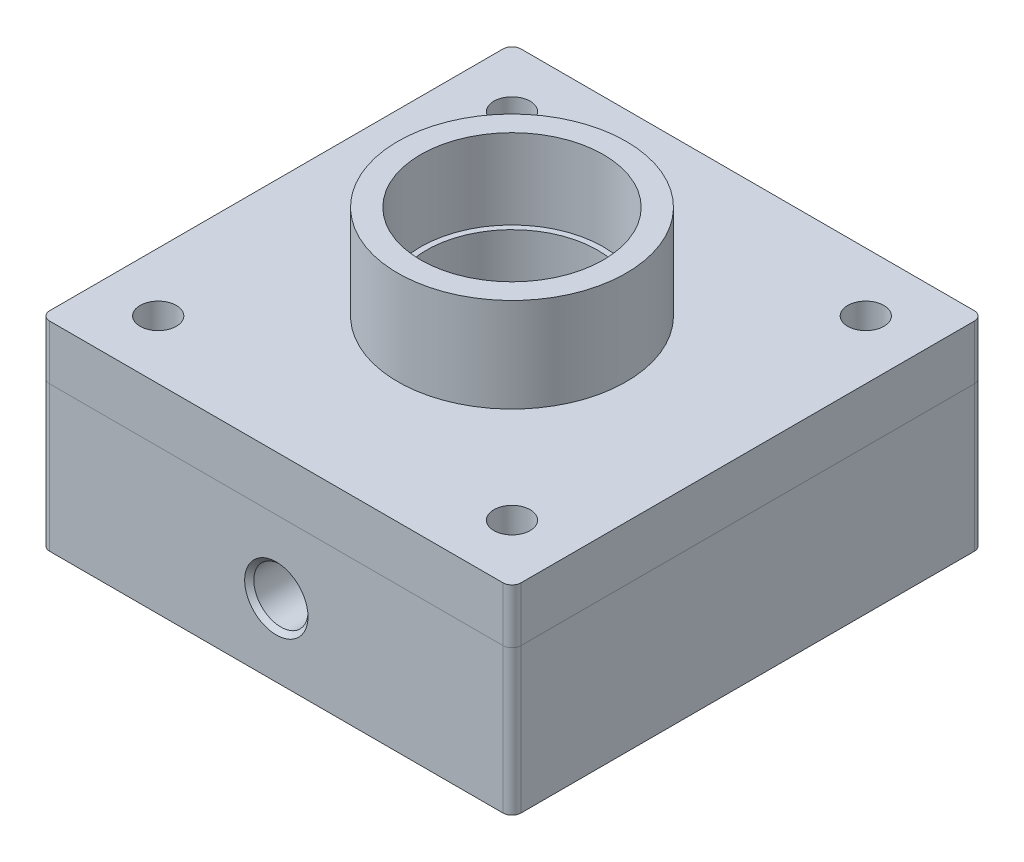
SolidWorks part; units mm, degrees
ref_plane "Front Plane" through (0, 0, 0) normal (0, 0, 1) x (1, 0, 0)
ref_plane "Top Plane" through (0, 0, 0) normal (0, 1, 0) x (1, 0, 0)
ref_plane "Right Plane" through (0, 0, 0) normal (1, 0, 0) x (0, 0, -1)
sketch "Sketch1" plane through (0, 0, 0) normal (0, 1, 0) x (1, 0, 0)
  line L1 (-82.55, 82.55) -> (82.55, 82.55)
  line L2 (-82.55, 82.55) -> (-82.55, -82.55)
  line L3 (-82.55, -82.55) -> (82.55, -82.55)
  line L4 (82.55, 82.55) -> (82.55, -82.55)
  line L5 (-82.55, 82.55) -> (82.55, -82.55) construction
  line L6 (-82.55, -82.55) -> (82.55, 82.55) construction
  point P0 (0, 0)
  dimension "D1" = 165.1
extrude "Boss-Extrude1" add sketch "Sketch1" along normal blind 50.8
sketch "Sketch2" plane through (0, 50.8, 0) normal (0, 1, 0) x (1, 0, 0)
  circle A0 centre (0, 0) radius 40
  dimension "D1" = 80
extrude "Boss-Extrude2" add sketch "Sketch2" along normal blind 52
sketch "Sketch3" plane through (0, 102.8, 0) normal (0, 1, 0) x (1, 0, 0)
  circle A0 centre (0, 0) radius 32
  dimension "D1" = 64
extrude "Cut-Extrude1" cut sketch "Sketch3" against normal blind 28
sketch "Sketch4" plane through (0, 74.8, 0) normal (0, 1, 0) x (1, 0, 0)
  circle A0 centre (0, 0) radius 30
  dimension "D1" = 60
extrude "Cut-Extrude2" cut sketch "Sketch4" against normal blind 22
fillet "Fillet1" radius 3.175 4 edges at (-82.55, 25.4, 82.55) (-82.55, 25.4, -82.55) (82.55, 25.4, -82.55) (82.55, 25.4, 82.55)
sketch "Sketch5" plane through (0, 0, 0) normal (0, -1, 0) x (1, 0, 0)
  circle A0 centre (0, 0) radius 20
  dimension "D1" = 40
extrude "Cut-Extrude3" cut sketch "Sketch5" against normal blind 40
sketch "Sketch6" plane through (0, 0, 0) normal (0, -1, 0) x (1, 0, 0)
  circle A0 centre (0, 0) radius 76.2
  circle A1 centre (0, 0) radius 69.85
  dimension "D1" = 152.4
  dimension "D2" = 139.7
extrude "Cut-Extrude4" cut sketch "Sketch6" against normal blind 8
sketch "Sketch7" plane through (0, 0, 82.55) normal (0, 0, 1) x (1, 0, 0)
  line L0 (-79.375, 25.4) -> (79.375, 25.4) construction
  line L1 (-79.375, 50.8) -> (-79.375, 0) construction
  line L2 (79.375, 0) -> (79.375, 50.8) construction
hole_wizard "1/2-14 NPSM Tapped Hole1" positions "Sketch8" profile "Sketch9" tap size "1/2-14 NPSM" standard "ANSI Inch"
sketch "Sketch8" plane through (0, 0, 82.55) normal (0, 0, 1) x (1, 0, 0)
  line L0 (-79.375, 25.4) -> (79.375, 25.4) construction
  point P0 (0, 25.4)
sketch "Sketch9" plane through (0, 25.4, 82.55) normal (1, 0, 0) x (0, -1, 0)
  line L0 (0, 0) -> (0, 52.9403)
  line L1 (0, 52.9403) -> (9.4869, 47.24)
  line L2 (9.4869, 47.24) -> (9.4869, 1.6002)
  line L3 (9.4869, 1.6002) -> (11.0871, 0)
  line L5 (11.0871, 0) -> (0, 0)
  line L6 (-9.4869, 1.6002) -> (-11.0871, 0) construction
  line L10 (0, 52.9403) -> (-9.4869, 47.24) construction
  line L11 (0, -6.35) -> (0, 107.95) construction
  dimension "Tap Drill Dia." = 18.9738
  dimension "Tap Drill Depth" = 47.24
  dimension "Near C'Sink Dia." = 22.1742
  dimension "Near C'Sink Angle" = 90
  dimension "Drill Angle" = 118
cosmetic thread "Hole Thread1" parameters "D1"=41.91, "D2"=20.9042
sketch "Sketch10" plane through (0, 0, 0) normal (0, -1, 0) x (1, 0, 0)
  line L0 (-79.375, 82.55) -> (79.375, 82.55) construction
  circle A0 centre (0, 50.55) radius 6.35
  dimension "D1" = 12.7
  dimension "D2" = 32
extrude "Cut-Extrude5" cut sketch "Sketch10" against normal blind 25
sketch "Sketch11" plane through (0, 0, 0) normal (0, -1, 0) x (1, 0, 0)
  line L1 (61.9638, -61.9638) -> (-61.9638, -61.9638) construction
  line L2 (61.9638, -61.9638) -> (61.9638, 61.9638) construction
  line L3 (61.9638, 61.9638) -> (-61.9638, 61.9638) construction
  line L4 (-61.9638, -61.9638) -> (-61.9638, 61.9638) construction
  line L5 (61.9638, -61.9638) -> (-61.9638, 61.9638) construction
  line L6 (61.9638, 61.9638) -> (-61.9638, -61.9638) construction
  circle A0 centre (0, 0) radius 87.63 construction
  circle A1 centre (-61.9638, 61.9638) radius 6.35
  circle A2 centre (61.9638, 61.9638) radius 6.35
  circle A3 centre (61.9638, -61.9638) radius 6.35
  circle A4 centre (-61.9638, -61.9638) radius 6.35
  dimension "D1" = 175.26
  dimension "D2" = 12.7
extrude "Cut-Extrude6" cut sketch "Sketch11" against normal through all
sketch "Sketch12" plane through (0, 50.8, 0) normal (0, 1, 0) x (1, 0, 0)
  line L4 (-82.55, 79.375) -> (-82.55, -79.375)
  line L5 (-79.375, -82.55) -> (79.375, -82.55)
  line L6 (82.55, -79.375) -> (82.55, 79.375)
  line L7 (79.375, 82.55) -> (-79.375, 82.55)
  line L8 (-82.55, 79.375) -> (-82.55, -79.375)
  line L9 (-79.375, -82.55) -> (79.375, -82.55)
  line L10 (82.55, -79.375) -> (82.55, 79.375)
  line L11 (79.375, 82.55) -> (-79.375, 82.55)
  circle A0 centre (0, 0) radius 40 construction
  circle A1 centre (61.9638, -61.9638) radius 6.35 construction
  circle A2 centre (61.9638, 61.9638) radius 6.35 construction
  circle A3 centre (-61.9638, 61.9638) radius 6.35 construction
  arc A4 (-82.55, -79.375) -> (-79.375, -82.55) centre (-79.375, -79.375) ccw
  arc A5 (79.375, -82.55) -> (82.55, -79.375) centre (79.375, -79.375) ccw
  arc A6 (82.55, 79.375) -> (79.375, 82.55) centre (79.375, 79.375) ccw
  arc A7 (-79.375, 82.55) -> (-82.55, 79.375) centre (-79.375, 79.375) ccw
  arc A8 (-82.55, -79.375) -> (-79.375, -82.55) centre (-79.375, -79.375) ccw
  arc A9 (79.375, -82.55) -> (82.55, -79.375) centre (79.375, -79.375) ccw
  arc A10 (82.55, 79.375) -> (79.375, 82.55) centre (79.375, 79.375) ccw
  arc A11 (-79.375, 82.55) -> (-82.55, 79.375) centre (-79.375, 79.375) ccw
  circle A12 centre (-61.9638, -61.9638) radius 6.35 construction
  circle A13 centre (0, 0) radius 40
  circle A14 centre (61.9638, -61.9638) radius 6.35
  circle A15 centre (61.9638, 61.9638) radius 6.35
  circle A16 centre (-61.9638, 61.9638) radius 6.35
  circle A17 centre (-61.9638, -61.9638) radius 6.35
  dimension "D1" = 0
extrude "Boss-Extrude3" add sketch "Sketch12" along normal blind 19.05 separate body
